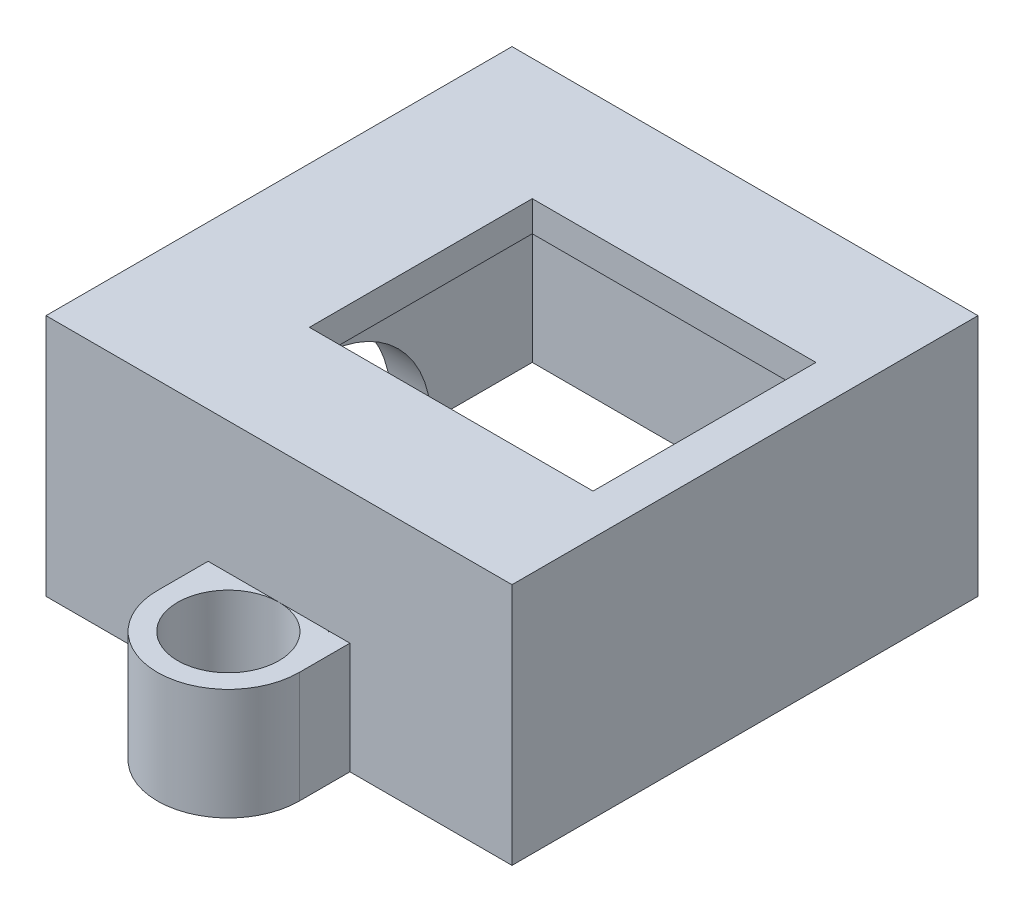
SolidWorks part; units mm, degrees
ref_plane "Plano frontal" through (0, 0, 0) normal (0, 0, 1) x (1, 0, 0)
ref_plane "Plano superior" through (0, 0, 0) normal (0, 1, 0) x (1, 0, 0)
ref_plane "Plano direito" through (0, 0, 0) normal (1, 0, 0) x (0, 0, -1)
sketch "Esboço1" plane through (0, 0, 0) normal (0, 1, 0) x (1, 0, 0)
  line L0 (0, 0) -> (0, -21)
  line L1 (0, -21) -> (19, -21)
  line L2 (19, -21) -> (19, 21)
  line L3 (19, 21) -> (-19, 21)
  line L4 (-19, 21) -> (-19, -21)
  line L5 (-19, -21) -> (0, -21)
  line L6 (4.899, -23) -> (5, -23)
  line L7 (21, -23) -> (21, 23)
  line L8 (23, 23) -> (-23, 23)
  line L9 (-21, 23) -> (-21, -23)
  line L10 (-23, -23) -> (-7, -23)
  line L11 (0, -21) -> (0, -28)
  line L12 (0, -28) -> (5, -28)
  line L13 (5, -23.101) -> (5, -21)
  line L14 (-7, -28) -> (-7, -23)
  line L15 (7, -28) -> (7, -23)
  line L16 (7, -23) -> (23, -23)
  line L17 (0, 0) -> (19, 0)
  line L18 (0, -23) -> (21, -23) construction
  line L19 (-21, -23) -> (0, -23) construction
  line L20 (-23, 23) -> (-23, -23)
  line L21 (23, -23) -> (23, 23)
  line L22 (21, 23) -> (-21, 23) construction
  line L23 (-7, -23) -> (7, -23)
  line L24 (7, 28) -> (7, 23)
  line L25 (-7, 28) -> (-7, 23)
  line L26 (-7, 23) -> (7, 23)
  circle A0 centre (0, -28) radius 5
  arc A1 (-7, -28) -> (7, -28) centre (0, -28) ccw
  arc A2 (5, -23.101) -> (4.899, -23) centre (0, -28) ccw
  arc A3 (-7, 28) -> (7, 28) centre (0, 28) cw
  circle A4 centre (0, 28) radius 5
  dimension "D1" = 2
  dimension "D2" = 2
  dimension "D3" = 2
extrude "Ressalto-extrusão1" add sketch "Esboço1" along normal blind 10 contours L10 L23 L11 L5 L4 L3 L2 L1 L13 L16 L7 L8 L26 L9 | L11 L23 L6 L13 L1 | L8 L20 L10 L9 | L16 L21 L8 L7 region at (-0.6229, 0, 22) region at (2.5, 0, 22) region at (-22, 0, 0) region at (22, 0, 0)
sketch "Esboço2" plane through (0, 10, 0) normal (0, 1, 0) x (1, 0, 0)
  line L0 (-9, 11) -> (19, 11)
  line L1 (-23, 23) -> (23, 23)
  line L2 (-23, 23) -> (-23, -23)
  line L3 (-23, -23) -> (23, -23)
  line L4 (23, 23) -> (23, -23)
  line L5 (-19, 21) -> (19, 21)
  line L6 (-19, 21) -> (-19, -21)
  line L7 (-19, -21) -> (19, -21)
  line L8 (19, 21) -> (19, -21)
  line L9 (9, 11) -> (9, -11)
  line L10 (-9, -11) -> (19, -11)
  line L11 (-9, 11) -> (-9, -11)
  line L12 (-9, 11) -> (9, 11) construction
  line L13 (-9, -11) -> (9, -11) construction
  line M13 (-23, -23) -> (23, -23)
  line M14 (23, -23) -> (23, 23)
  line M15 (23, 23) -> (-23, 23)
  line M16 (-23, 23) -> (-23, -23)
  line M17 (19, 21) -> (19, -21)
  line M18 (19, -21) -> (-19, -21)
  line M19 (-19, -21) -> (-19, 21)
  line M20 (-19, 21) -> (19, 21)
  dimension "D1" = 10
extrude "Ressalto-extrusão2" add sketch "Esboço2" along normal blind 3 contours L8 M16 M13 M14 M15 M20 M17 M18 M19 | L11 L0 L8 L10 M17 M20 M19 M18 region at (-9.5664, 10, 0) region at (0, 10, -22.3495)
extrude "Ressalto-extrusão3" add sketch "Esboço1<4>" against normal blind 11 contours L10 L23 L11 L5 L4 L3 L2 L1 L13 L16 L7 L8 L26 L9 | L13 A2 L23 A0 L14 A1 L15 | L11 L23 L6 L13 L1 | L16 L21 L8 L7 | L26 A4 L8 L24 A3 L25 | L8 L20 L10 L9 region at (-0.6229, 0, 22) region at (2.5, 0, 22) region at (2.4495, 0, 23.1844) region at (-22, 0, 0) region at (22, 0, 0) region at (-6.8156, 0, -25.5)
sketch "Esboço1<4>" plane through (0, 0, 0) normal (0, 1, 0) x (1, 0, 0) same geometry as "Esboço1"
sketch "Esboço3" plane through (-23, 0, 0) normal (-1, 0, 0) x (0, 0, 1)
  line L0 (-23, -11) -> (23, -11) construction
  circle A0 centre (0, -11) radius 11
extrude "Corte-extrusão1" cut sketch "Esboço3" against normal blind 11
